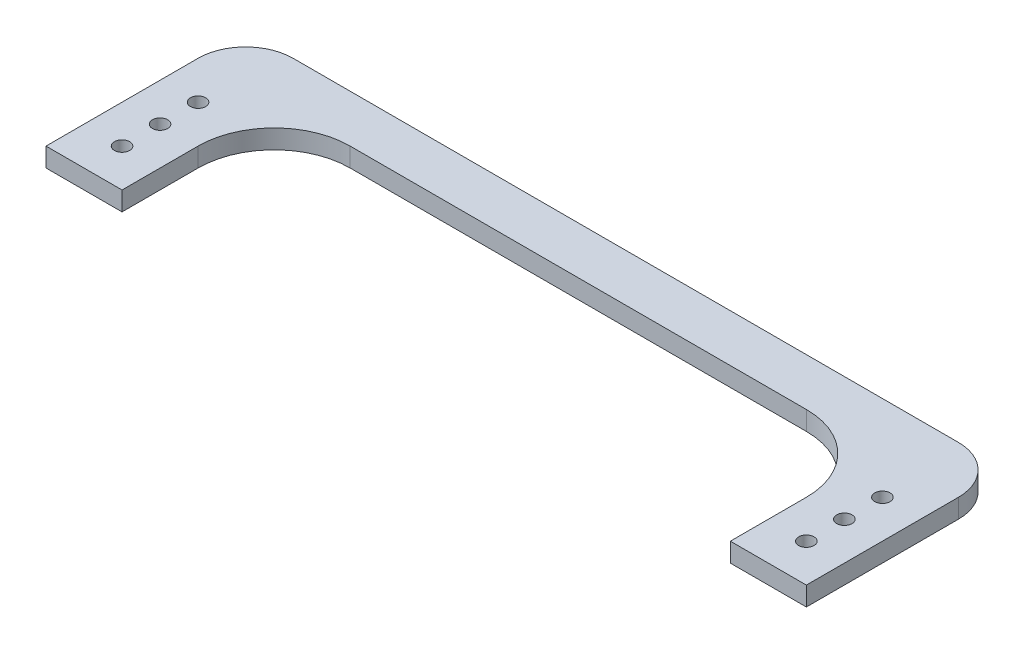
SolidWorks part; units mm, degrees
material "6061-T6 (SS)"
ref_plane "Front" through (0, 0, 0) normal (0, 0, 1) x (1, 0, 0)
ref_plane "Top" through (0, 0, 0) normal (0, 1, 0) x (1, 0, 0)
ref_plane "Right" through (0, 0, 0) normal (1, 0, 0) x (0, 0, -1)
sketch "Sketch1" plane through (0, 0, 0) normal (0, 1, 0) x (1, 0, 0)
  line L0 (-101.6, -25.4) -> (-101.6, 0)
  line L1 (101.6, 0) -> (101.6, -25.4)
  line L2 (101.6, -25.4) -> (127, -25.4)
  line L3 (0, 0) -> (0, -66.2098) construction
  line L4 (-101.6, -25.4) -> (-127, -25.4)
  line L5 (-127, -25.4) -> (-127, 25.4)
  line L6 (127, 25.4) -> (127, -25.4)
  line L8 (-76.2, 25.4) -> (76.2, 25.4)
  line L12 (111.125, 41.275) -> (-111.125, 41.275)
  line L14 (127, 6.8059) -> (127, -25.4) construction
  line L15 (-127, -25.4) -> (-127, 6.8059) construction
  arc A6 (85.728, 9.9217) -> (101.6, 0) centre (81.1476, -15.0619) cw construction
  arc A7 (-127, 6.8059) -> (-87.8514, 57.3252) centre (57.0959, -95.4263) cw construction
  arc A8 (-87.8514, 57.3252) -> (90.3083, 34.9053) centre (-198.2524, -1539.0619) cw construction
  arc A9 (90.3083, 34.9053) -> (127, 6.8059) centre (81.1476, -15.0619) cw construction
  arc A10 (-101.6, 0) -> (-78.0712, 31.1456) centre (57.0959, -95.4263) cw construction
  arc A11 (-78.0712, 31.1456) -> (85.728, 9.9217) centre (-198.2524, -1539.0619) cw construction
  arc A13 (127, 25.4) -> (111.125, 41.275) centre (111.125, 25.4) ccw
  arc A15 (-111.125, 41.275) -> (-127, 25.4) centre (-111.125, 25.4) ccw
  arc A16 (76.2, 25.4) -> (101.6, 0) centre (76.2, 0) cw
  arc A17 (-101.6, 0) -> (-76.2, 25.4) centre (-76.2, 0) cw
  point P10 (209.55, 1.0124)
  point P27 (235.7287, -6.8059)
  point P28 (-209.55, 0)
  point P31 (-234.95, -5.9568)
  point P32 (-209.55, 0.6129)
  point P34 (-209.55, -43.5385)
  point P36 (-186.2949, 50.8)
  point P37 (-234.95, 18.4642)
  dimension "D9" = 25.4
  dimension "D1" = 203.2
  dimension "D2" = 50.8
  dimension "D6" = 15.875
  dimension "D3" = 25.4
extrude "Boss-Extrude1" add sketch "Sketch1" along normal blind 6.35
hole_wizard "#10 Clearance Hole1" positions "Sketch2" profile "Sketch3" hole size "#10" standard "ANSI Inch" end condition through all
sketch "Sketch2" plane through (0, 6.35, 0) normal (0, 1, 0) x (1, 0, 0)
  line L3 (-127, -25.4) -> (-114.3, -12.7) construction
  line L4 (-114.3, -12.7) -> (-114.3, 0) construction
  line L5 (-114.3, 0) -> (-114.3, 12.7) construction
  line L6 (-114.3, 12.7) -> (-101.6, 25.4) construction
  line L8 (0, 0) -> (0, -50.8) construction
  line L9 (-101.6, -25.4) -> (-101.6, 0) construction
  line L10 (-76.2, 25.4) -> (76.2, 25.4) construction
  point P0 (-114.3, -12.7)
  point P2 (-114.3, 0)
  point P4 (-114.3, 12.7)
  point P29 (114.3, 12.7)
  point P30 (114.3, 0)
  point P31 (114.3, -12.7)
  point P33 (0, 0)
  point P34 (-212.0122, 17.8814)
  dimension "D1" = 12.7
sketch "Sketch3" plane through (-114.3, 6.35, 12.7) normal (1, 0, 0) x (0, 0, 1)
  line L0 (0, 0) -> (0, 6.35)
  line L1 (0, 6.35) -> (2.5527, 6.35)
  line L2 (2.5527, 6.35) -> (2.5527, 0)
  line L5 (2.5527, 0) -> (0, 0)
  line L11 (0, -6.35) -> (0, 107.95) construction
  dimension "Thru Hole Dia." = 5.1054
  dimension "Thru Hole Depth" = 6.35
